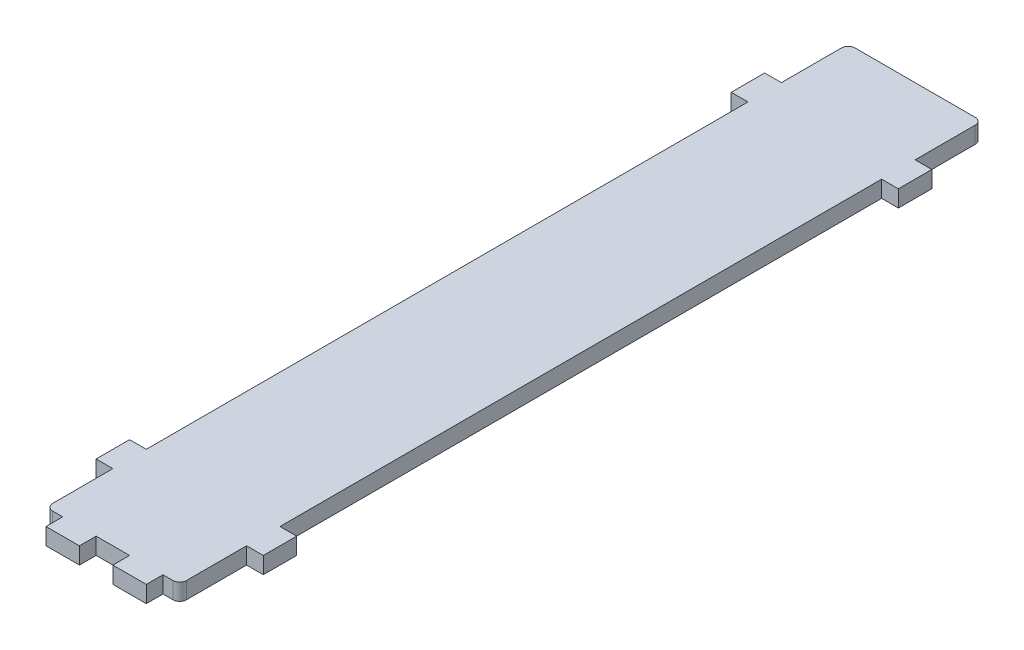
SolidWorks part; units mm, degrees
material "Beech"
ref_plane "Front Plane" through (0, 0, 0) normal (0, 0, 1) x (1, 0, 0)
ref_plane "Top Plane" through (0, 0, 0) normal (0, 1, 0) x (1, 0, 0)
ref_plane "Right Plane" through (0, 0, 0) normal (1, 0, 0) x (0, 0, -1)
sketch "Sketch1" plane through (0, 0, 0) normal (0, 1, 0) x (1, 0, 0)
  line L0 (0, 0) -> (6.35, 0)
  line L1 (6.35, 0) -> (6.35, -6.35)
  line L2 (6.35, -6.35) -> (19.05, -6.35)
  line L3 (19.05, -6.35) -> (19.05, 0)
  line L4 (19.05, 0) -> (31.75, 0)
  line L5 (31.75, 0) -> (31.75, -6.35)
  line L6 (31.75, -6.35) -> (44.45, -6.35)
  line L7 (44.45, -6.35) -> (44.45, 0)
  line L8 (44.45, 0) -> (50.8, 0)
  line L9 (50.8, 0) -> (50.8, 25.4)
  line L10 (50.8, 304.8) -> (0, 304.8)
  line L11 (0, 304.8) -> (0, 279.4)
  line L12 (50.8, 25.4) -> (57.15, 25.4)
  line L13 (57.15, 25.4) -> (57.15, 38.1)
  line L14 (57.15, 38.1) -> (50.8, 38.1)
  line L15 (50.8, 38.1) -> (50.8, 266.7)
  line L16 (50.8, 266.7) -> (57.15, 266.7)
  line L17 (57.15, 266.7) -> (57.15, 279.4)
  line L18 (57.15, 279.4) -> (50.8, 279.4)
  line L19 (50.8, 279.4) -> (50.8, 304.8)
  line L20 (0, 25.4) -> (-6.35, 25.4)
  line L22 (-6.35, 25.4) -> (-6.35, 38.1)
  line L23 (0, 38.1) -> (-6.35, 38.1)
  line L24 (0, 279.4) -> (-6.35, 279.4)
  line L25 (0, 25.4) -> (0, 0)
  line L26 (-6.35, 279.4) -> (-6.35, 266.7)
  line L27 (0, 266.7) -> (-6.35, 266.7)
  line L28 (0, 266.7) -> (0, 38.1)
  dimension "D1" = 12.7
  dimension "D2" = 6.35
  dimension "D3" = 25.4
  dimension "D4" = 25.4
  dimension "D5" = 6.35
  dimension "D6" = 304.8
  dimension "D7" = 50.8
  dimension "D8" = 25.4
  dimension "D9" = 6.35
extrude "Side Plate" add sketch "Sketch1" along normal blind 6.35
fillet "Fillet1" radius 2.54 4 edges at (50.8, 3.175, 0) (50.8, 3.175, -304.8) (0, 3.175, -304.8) (0, 3.175, 0)
equation "\"CageLeftBottomEdge\"=22.11mm"
equation "\"CageLeftTopEdge\"=22.11mm"
equation "\"CageRightBottomEdge\"=21.63mm"
equation "\"CageRightTopEdge\"=21.63mm"
equation "\"CageHeight\"=86.04mm"
equation "\"CageLength\"=73.76mm"
equation "\"CageTopScrewClearance\"=10mm"
equation "\"CageBottomScrewClearance\"=25mm"
equation "\"CageLeftTopDepth\"= 11.65mm"
equation "\"CageLeftBottomDepth\"=11.11mm"
equation "\"CageLeftTopHeight\"=8.56175mm"
equation "\"CageLeftBottomHeight\"=16mm"
equation "\"CageRightTopDepth\"= 11.05mm"
equation "\"CageRightBottomDepth\"=10.58mm"
equation "\"CageRightTopHeight\"=9.6mm"
equation "\"CageRightBottomHeight\"=15.49mm"
equation "\"CageLeftTopChannelDepth\"=2.41908mm"
equation "\"CageLeftBottomChannelDepth\"=2.588mm"
equation "\"CageLeftChannelHeight\"=11.7mm"
equation "\"CageRightTopChannelDepth\"=2.32mm"
equation "\"CageRightBottomChannelDepth\"=2.318mm"
equation "\"CageRightChannelHeight\"=10mm"
equation "\"CageChanRelHeight\"=23.99mm"
equation "\"CageChanRelDepth\"=5.492mm"
equation "\"CageChamberRadius\"=16.261mm"
equation "\"CageScrewDiameter\"=4.8mm"
equation "\"CageSetScrewDiameter\"=3.5mm"
equation "\"CageAxleRadius\"=6.639mm"
equation "\"CageAxleKeyHeight\"=1.619mm"
equation "\"CageAxleKeyWidth\"=2.662mm"
equation "\"CageHoseWindowWidth\"=16.29mm"
equation "\"CageHoseWindowHeight\"=26.5mm"
equation "\"CageHoseWindow-Edge\"=8.89mm"
equation "\"CageScrew-VerticalEdge\"=5.0mm"
equation "\"CageScrew-HorizontalEdge\"=7.5mm"
equation "\"CageScrew-HoseCornerScrewEdge\"=4.45mm"
equation "\"CageAxle-BottomEdge\"=56.05mm"
equation "\"CageAxle-FrontEdge\"=46.03mm"
equation "\"CageBackSetScrew-Axle\"=40mm"
equation "\"CageFrontSetScrew-Axle\"=22mm"
equation "\"CageVelocityWindow-BackEdge\"=34.8mm"
equation "\"CageVelocityWindow-BottomEdge\"=27.55mm"
equation "\"CageVelocityWindowHeight\"=22.29mm"
equation "\"CageVelocityWindowWidth\"=12.61mm"
equation "\"TriggerSlot-BottomEdge\"=6.35mm"
equation "\"TriggerSlot-FrontEdge\"=15mm"
equation "\"TriggerSlotSize\"=6.7mm"
equation "\"TriggerRackOffset\"=.236224in"
equation "\"TriggerSlotSizeInt\"=.25in"
equation "\"MotorMountLegLength\"=.25in"
equation "\"GearOffset\"=.264907in"
equation "\"TriggerSlotSpacing\"=.25in"
equation "\"TriggerMiniSlotWidth\"=3.5mm"
equation "\"TriggerRackWidth\"=6.5mm"
equation "\"whitemotordepth\"=11.27mm"
equation "\"whitemotorbackdepth\"=3.845mm"
equation "\"whitemotoraxledepth\" = 3.5mm"
equation "\"whitemotoraxleoffset\"=11.4mm"
equation "\"whitemotorwidth\"=12.07mm"
equation "\"whitemotorheight\"=16.68mm"
equation "\"whitemotorcylinderlength\" =13.04mm"
equation "\"whitemotorcylinderradius\"=3.845mm"
equation "\"whitemotorcylinderoffset\"=2.35mm"
equation "\"whitemotorcutoutlength\"=1.88mm"
equation "\"whitemotorouterrad\"=5mm"
equation "\"whitemotorinnerrad\"=2.95mm"
equation "\"elasticracklength\"=2in"
equation "\"elasticrackpegsize\"=.25in"
equation "\"elasticrackpegbuffer\"=.125in"
equation "\"elasticrackpegspacing\"=1.76476378in"
equation "\"elasticbaybuffer\"=.25in"
equation "\"elasticdepth\"=.125in"
equation "\"elasticbaydepth\"=.75in"
equation "\"motormountwidth\"=12mm"
equation "\"motormountcornerfillet\"=3mm"
equation "\"pandiscradius\"=14in"
equation "\"towermaterialwidth\"=.25in"
equation "\"towerslotlength\"=.5in"
equation "\"towermarkerspace\"=5in"
equation "\"towerslothorizoffset\"=1in"
equation "\"towerslothorizspacing\"=2in"
equation "\"towerslotvertoffset\"=3in"
equation "\"D1@Sketch1\"=\"towerslotlength\""
equation "\"D2@Sketch1\"=\"towermaterialwidth\""
equation "\"towerupslot\"=1in"
equation "\"D3@Sketch1\"=\"towerupslot\""
equation "\"towerslotvertspacing\"=1in"
equation "\"D4@Sketch1\"=\"towerslotvertspacing\""
equation "\"D5@Sketch1\"=\"towerslotlength\"/2"
equation "\"towerheight\"=12in"
equation "\"D6@Sketch1\"=\"towerheight\""
equation "\"D7@Sketch1\"=2*\"towerslotlength\"+\"towerslotvertspacing\""
equation "\"D8@Sketch1\"=\"towerupslot\""
equation "\"D9@Sketch1\"=\"towerslotvertoffset\"-(\"towermarkerspace\"/2)-\"towermaterialwidth\""
equation "\"D1@Side Plate\"=\"towermaterialwidth\""
equation "\"toweraxle\"=.5in"
equation "\"stepperouterrad\"=10mm"
equation "\"stepperscrewsize\"=3.45mm"
equation "\"stepperscrewc2c\"=49.5mm"
equation "\"stepperdepthoffset\"=24mm"
equation "\"stepperhorizoffset\"=22.91mm"
equation "\"shaftslotOD\"=18.8mm"
equation "\"shaftslotID\"=13.28mm"
equation "\"shaftkeywidth\"=2.67mm"
equation "\"shaftkeydepth\"=1.8mm"
equation "\"shaftcollartotaldepth\"=12.5mm"
equation "\"shaftsquaredepth\"=6mm"
equation "\"shaftsetscrewsize\"=3.5mm"
equation "\"shaftkeytightdepth\"=1.85mm"
equation "\"shaftslottightID\"=12.78mm"
equation "\"shaftsetscrewoffset\"=9mm"
equation "\"cagecollartotaldepth\"=10mm"
equation "\"cagecollartotalwidth\"=35mm"
equation "\"cagecollarbasedepth\"=4mm"
equation "\"gearhubintdiam\"=30mm"
equation "\"gearhubintwid\"=15mm"
equation "\"towerspeedwidth\"=2in"
equation "\"towerspeedheight\"=8in"
equation "\"towerspeedgap\"=2in"
equation "\"stepperaxleflat\"=.037in"
equation "\"stepperaxlerad\"=0.11811024in"
equation "\"ajaxaxlesize\"=3.87mm"
equation "\"ajaxinnercut\"=2.3mm"
equation "\"ajaxwidth\"=6.1mm"
equation "\"ajaxdiametral\"=25.8854"
equation "\"ajaxcutoutdepth\"=2.3mm"
equation "\"ajax4020gap\"=29.5mm"
equation "\"ajax4010gap\"=24.5mm"
equation "\"ajax20hubbuffer\"=6.1mm"
equation "\"ajax20hubholeoffset\"=.19685in"
equation "\"ajax20hubholesize\"=.059055in"
equation "\"ajax20cutoutint\"=13.4mm"
equation "\"ajax40hubholesize\"=7.21mm"
equation "\"ajax40hubholeoffset\"=10mm"
equation "\"ajax40hubbuffer\"=8.9mm"
equation "\"ajax40cutoutint\"=32.6mm"
equation "\"bearingpandiscrad\"=6.8in"
equation "\"bearingpandiscang\"=48.75deg"
equation "\"bearingclearholedist\"=4.7345in"
equation "\"bearingclearholesize\"=.5in"
equation "\"bearingclearholeang\"=22.5deg"
equation "\"bearingmountholedist\"=4.25in"
equation "\"bearingwirehole\"=1.5in"
equation "\"no6diam\"=.146in"
equation "\"shortconangle\"=20deg"
equation "\"shortconlen\"=.875in"
equation "\"longconlen\"=1.25in"
equation "\"longconangle\"=15deg"
